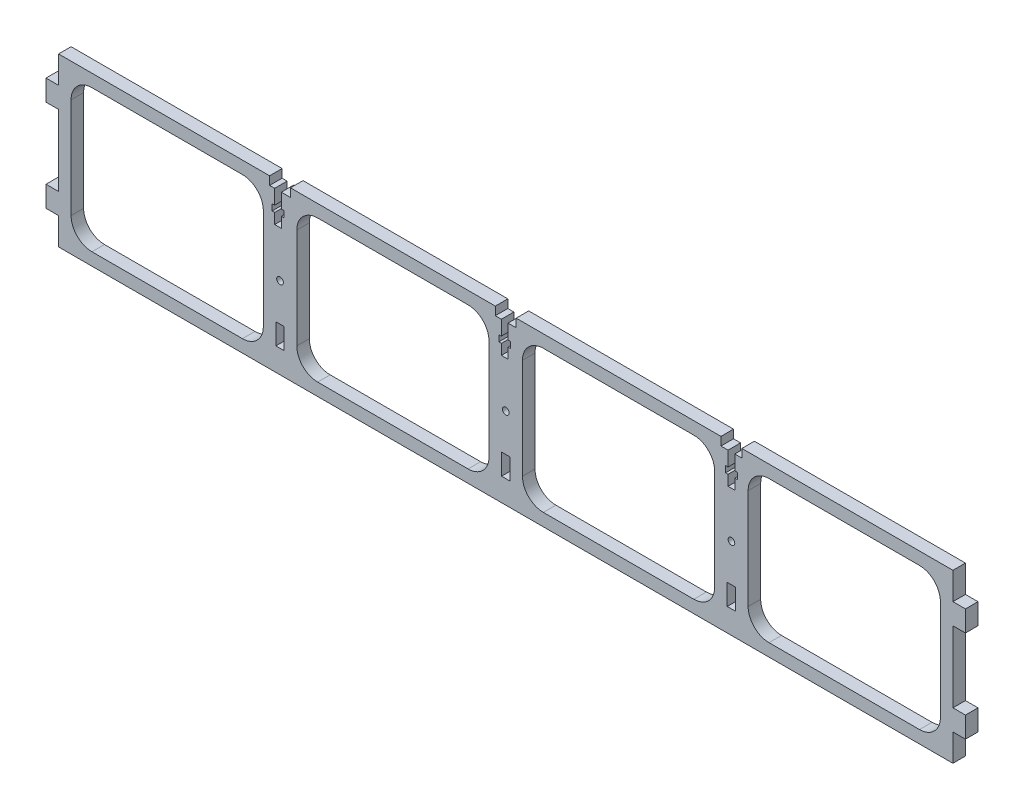
SolidWorks part; units mm, degrees
ref_plane "Front Plane" through (0, 0, 0) normal (0, 0, 1) x (1, 0, 0)
ref_plane "Top Plane" through (0, 0, 0) normal (0, 1, 0) x (1, 0, 0)
ref_plane "Right Plane" through (0, 0, 0) normal (1, 0, 0) x (0, 0, -1)
sketch "Sketch1" plane through (0, 0, 0) normal (0, 0, 1) x (1, 0, 0)
  line L1 (-214, -40) -> (214, -40)
  line L2 (-214, -40) -> (-214, 40)
  line L3 (-214, 40) -> (214, 40)
  line L4 (214, -40) -> (214, 40)
  line L5 (-214, -40) -> (214, 40) construction
  line L6 (-214, 40) -> (214, -40) construction
  point P0 (0, 0)
  dimension "D1" = 428
  dimension "D2" = 80
extrude "Boss-Extrude1" add sketch "Sketch1" along normal blind 6
sketch "Sketch2" plane through (0, 0, 6) normal (0, 0, 1) x (1, 0, 0)
  line L0 (-116, -42) -> (-116, -29) construction
  line L1 (-208, 40) -> (-208, -40) construction
  line L2 (-214, -34) -> (214, -34) construction
  line L3 (-214, -40) -> (214, -40) construction
  line L8 (214, -40) -> (214, 40)
  line L9 (214, 40) -> (-214, 40)
  line L10 (-214, 40) -> (-214, -40)
  line L11 (-214, -40) -> (214, -40)
  line L12 (214, -40) -> (214, 40) construction
  line L13 (214, 40) -> (-214, 40)
  line L14 (-214, 40) -> (-214, -40) construction
  line L15 (-208, -40) -> (214, -40) construction
  line L16 (-110, -42) -> (-110, -29) construction
  line L17 (-110, -42) -> (-110, -29) construction
  line L18 (-116, -24) -> (-116, 24)
  line L19 (-198, -34) -> (-126, -34)
  line L20 (-208, 24) -> (-208, -24)
  line L21 (-126, 34) -> (-198, 34)
  arc A0 (-198, 34) -> (-208, 24) centre (-198, 24) ccw
  arc A1 (-126, 34) -> (-116, 24) centre (-126, 24) cw
  arc A2 (-116, -24) -> (-126, -34) centre (-126, -24) cw
  arc A3 (-198, -34) -> (-208, -24) centre (-198, -24) cw
  dimension "D6" = 10
  dimension "D5" = 6
  dimension "D1" = 0
  dimension "D2" = 6
  dimension "D3" = 6
  dimension "D4" = 6
extrude "Cut-Extrude1" cut sketch "Sketch2" against normal up to next contours L18 L21 L20 L19 region at (-162, 0, 6)
pattern_linear "LPattern1" count 4 spacing 108 along (1, 0, 0) of "Cut-Extrude1"
sketch "Sketch3" plane through (0, 0, 0) normal (0, 0, -1) x (-1, 0, 0)
  line L8 (-110, -29) -> (-110, -19) construction
  line L9 (-110, -19) -> (-106, -19) construction
  line L10 (-106, -19) -> (-106, -29) construction
  line L11 (-106, -29) -> (-110, -29) construction
  line L24 (-110, -29) -> (-110, -19)
  line L25 (-110, -19) -> (-106, -19)
  line L26 (-106, -19) -> (-106, -29)
  line L27 (-106, -29) -> (-110, -29)
  line L44 (-2, -29) -> (-2, -19) construction
  line L45 (-2, -19) -> (2, -19) construction
  line L46 (2, -19) -> (2, -29) construction
  line L47 (2, -29) -> (-2, -29) construction
  line L52 (-2, -29) -> (-2, -19)
  line L53 (-2, -19) -> (2, -19)
  line L54 (2, -19) -> (2, -29)
  line L55 (2, -29) -> (-2, -29)
  line L60 (106, -29) -> (106, -19) construction
  line L61 (106, -19) -> (110, -19) construction
  line L62 (110, -19) -> (110, -29) construction
  line L63 (110, -29) -> (106, -29) construction
  line L68 (106, -29) -> (106, -19)
  line L69 (106, -19) -> (110, -19)
  line L70 (110, -19) -> (110, -29)
  line L71 (110, -29) -> (106, -29)
  circle A3 centre (108, -1) radius 1.6 construction
  circle A4 centre (0, -1) radius 1.6 construction
  circle A5 centre (-108, -1) radius 1.6 construction
  circle A6 centre (108, -1) radius 1.6
  circle A7 centre (0, -1) radius 1.6
  circle A8 centre (-108, -1) radius 1.6
extrude "Cut-Extrude2" cut sketch "Sketch3" against normal through all
sketch "Sketch4" plane through (0, 0, 0) normal (0, 0, -1) x (-1, 0, 0)
  line L0 (-111.5, 17) -> (-214, 17) construction
  line L1 (-214, -40) -> (-214, 40) construction
  line L2 (-108.5, 0) -> (-214, 0) construction
  line L3 (-220, 21.3321) -> (-220, 40) construction
  line L4 (-214, 17) -> (-220, 17)
  line L5 (-214, 17) -> (-214, 27)
  line L6 (-214, 27) -> (-220, 27)
  line L7 (-220, 17) -> (-220, 27)
  line L9 (-220, -17) -> (-220, -27)
  line L10 (-214, -27) -> (-220, -27)
  line L11 (-214, -17) -> (-214, -27)
  line L12 (-214, -17) -> (-220, -17)
  line L13 (0, 0) -> (0, 40) construction
  line L14 (-214, 40) -> (214, 40) construction
  line L15 (214, -17) -> (220, -17)
  line L16 (214, -17) -> (214, -27)
  line L17 (214, -27) -> (220, -27)
  line L18 (220, -17) -> (220, -27)
  line L19 (220, 17) -> (220, 27)
  line L20 (214, 27) -> (220, 27)
  line L21 (214, 17) -> (214, 27)
  line L22 (214, 17) -> (220, 17)
  point P13 (-108.5, -1)
  dimension "D1" = 34
  dimension "D2" = 10
extrude "Boss-Extrude2" add sketch "Sketch4" against normal blind 6
sketch "Sketch5" plane through (0, 40, 0) normal (0, 1, 0) x (1, 0, 0)
  line L0 (214, -6) -> (-214, -6) construction
  line L1 (-113, 0) -> (-103, 0)
  line L2 (-113, 0) -> (-113, -6)
  line L3 (-113, -6) -> (-103, -6)
  line L4 (-103, 0) -> (-103, -6)
  line L5 (-113, 0) -> (-103, -6) construction
  line L6 (-113, -6) -> (-103, 0) construction
  line L7 (-103, -6) -> (-103, 0) construction
  line L8 (5, -6) -> (5, 0) construction
  line L9 (-5, 0) -> (5, 0)
  line L10 (-5, 0) -> (-5, -6)
  line L11 (-5, -6) -> (5, -6)
  line L12 (5, 0) -> (5, -6)
  line L13 (-5, 0) -> (5, -6) construction
  line L14 (-5, -6) -> (5, 0) construction
  line L15 (113, -6) -> (113, 0) construction
  line L16 (103, 0) -> (113, 0)
  line L17 (103, 0) -> (103, -6)
  line L18 (103, -6) -> (113, -6)
  line L19 (113, 0) -> (113, -6)
  line L20 (103, 0) -> (113, -6) construction
  line L21 (103, -6) -> (113, 0) construction
  point P0 (-108, -3)
  point P10 (0, -3)
  point P18 (108, -3)
extrude "Cut-Extrude3" cut sketch "Sketch5" against normal blind 4
sketch "Sketch6" plane through (0, 0, 0) normal (0, 0, -1) x (-1, 0, 0)
  line L12 (-109.6, 36) -> (-109.6, 29)
  line L13 (-106.4, 36) -> (-109.6, 36)
  line L14 (-106.4, 29) -> (-106.4, 36)
  line L15 (-105.2, 29) -> (-106.4, 29)
  line L16 (-105.2, 26) -> (-105.2, 29)
  line L17 (-106.4, 26) -> (-105.2, 26)
  line L18 (-106.4, 21) -> (-106.4, 26)
  line L19 (-109.6, 21) -> (-106.4, 21)
  line L20 (-109.6, 26) -> (-109.6, 21)
  line L21 (-110.8, 26) -> (-109.6, 26)
  line L22 (-110.8, 29) -> (-110.8, 26)
  line L23 (-109.6, 29) -> (-110.8, 29)
  line L24 (-109.6, 36) -> (-109.6, 29)
  line L25 (-106.4, 36) -> (-109.6, 36)
  line L26 (-106.4, 29) -> (-106.4, 36)
  line L27 (-105.2, 29) -> (-106.4, 29)
  line L28 (-105.2, 26) -> (-105.2, 29)
  line L29 (-106.4, 26) -> (-105.2, 26)
  line L30 (-106.4, 21) -> (-106.4, 26)
  line L31 (-109.6, 21) -> (-106.4, 21)
  line L32 (-109.6, 26) -> (-109.6, 21)
  line L33 (-110.8, 26) -> (-109.6, 26)
  line L34 (-110.8, 29) -> (-110.8, 26)
  line L35 (-109.6, 29) -> (-110.8, 29)
  line L36 (-1.1, 29) -> (-2.3, 29)
  line L37 (-2.3, 29) -> (-2.3, 26)
  line L38 (-2.3, 26) -> (-1.1, 26)
  line L39 (-1.1, 26) -> (-1.1, 21)
  line L40 (-1.1, 21) -> (2.1, 21)
  line L41 (2.1, 21) -> (2.1, 26)
  line L42 (2.1, 26) -> (3.3, 26)
  line L43 (3.3, 26) -> (3.3, 29)
  line L44 (3.3, 29) -> (2.1, 29)
  line L45 (2.1, 29) -> (2.1, 36)
  line L46 (2.1, 36) -> (-1.1, 36)
  line L47 (-1.1, 36) -> (-1.1, 29)
  line L48 (-1.1, 29) -> (-2.3, 29)
  line L49 (-2.3, 29) -> (-2.3, 26)
  line L50 (-2.3, 26) -> (-1.1, 26)
  line L51 (-1.1, 26) -> (-1.1, 21)
  line L52 (-1.1, 21) -> (2.1, 21)
  line L53 (2.1, 21) -> (2.1, 26)
  line L54 (2.1, 26) -> (3.3, 26)
  line L55 (3.3, 26) -> (3.3, 29)
  line L56 (3.3, 29) -> (2.1, 29)
  line L57 (2.1, 29) -> (2.1, 36)
  line L58 (2.1, 36) -> (-1.1, 36)
  line L59 (-1.1, 36) -> (-1.1, 29)
  line L60 (107.4, 36) -> (107.4, 29)
  line L61 (110.6, 36) -> (107.4, 36)
  line L62 (110.6, 29) -> (110.6, 36)
  line L63 (111.8, 29) -> (110.6, 29)
  line L64 (111.8, 26) -> (111.8, 29)
  line L65 (110.6, 26) -> (111.8, 26)
  line L66 (110.6, 21) -> (110.6, 26)
  line L67 (107.4, 21) -> (110.6, 21)
  line L68 (107.4, 26) -> (107.4, 21)
  line L69 (106.2, 26) -> (107.4, 26)
  line L70 (106.2, 29) -> (106.2, 26)
  line L71 (107.4, 29) -> (106.2, 29)
  line L72 (107.4, 36) -> (107.4, 29)
  line L73 (110.6, 36) -> (107.4, 36)
  line L74 (110.6, 29) -> (110.6, 36)
  line L75 (111.8, 29) -> (110.6, 29)
  line L76 (111.8, 26) -> (111.8, 29)
  line L77 (110.6, 26) -> (111.8, 26)
  line L78 (110.6, 21) -> (110.6, 26)
  line L79 (107.4, 21) -> (110.6, 21)
  line L80 (107.4, 26) -> (107.4, 21)
  line L81 (106.2, 26) -> (107.4, 26)
  line L82 (106.2, 29) -> (106.2, 26)
  line L83 (107.4, 29) -> (106.2, 29)
  dimension "D1" = 0
  dimension "D2" = 0
  dimension "D3" = 0
extrude "Cut-Extrude4" cut sketch "Sketch6" against normal up to next
